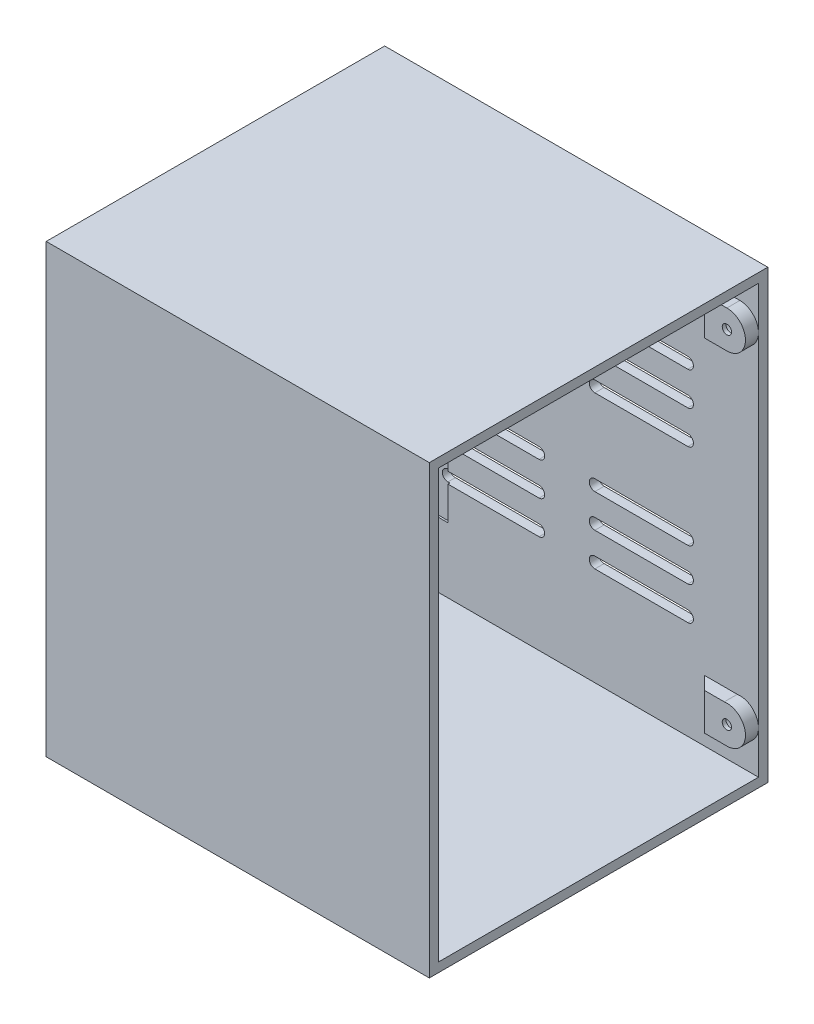
SolidWorks part; units mm, degrees
ref_plane "Front Plane" through (0, 0, 0) normal (0, 0, 1) x (1, 0, 0)
ref_plane "Top Plane" through (0, 0, 0) normal (0, 1, 0) x (1, 0, 0)
ref_plane "Right Plane" through (0, 0, 0) normal (1, 0, 0) x (0, 0, -1)
sketch "Sketch1" plane through (205.5525, 0, 0) normal (1, 0, 0) x (0, 0, -1)
  line L0 (1.5129, 48.8646) -> (1.513, -71.1354) construction
  line L1 (-89.4871, 48.8644) -> (1.5129, 48.8646) construction
  line L2 (-89.4871, 48.8644) -> (-89.487, -71.1356) construction
  line L3 (-89.487, -71.1356) -> (1.513, -71.1354) construction
  line L4 (1.5129, 48.8646) -> (1.513, -71.1354)
  line L5 (-89.4871, 48.8644) -> (1.5129, 48.8646)
  line L6 (-89.4871, 48.8644) -> (-89.487, -71.1356)
  line L7 (-89.487, -71.1356) -> (1.513, -71.1354)
  line L8 (-86.987, -68.6356) -> (-0.987, -68.6355)
  line L9 (-0.9871, 46.3645) -> (-0.987, -68.6355)
  line L10 (-86.9871, 46.3644) -> (-0.9871, 46.3645)
  line L11 (-86.9871, 46.3644) -> (-86.987, -68.6356)
  dimension "D1" = 2.5
extrude "Boss-Extrude1" add sketch "Sketch1" along normal up to surface (103 mm away)
sketch "Sketch2" plane through (0, 0, 86.9871) normal (0, 0, -1) x (-1, 0, 0)
  line L0 (-205.5525, 46.3645) -> (-205.5525, -68.6355) construction
  line L1 (-208.4525, -46.1353) -> (-206.5525, -46.1353)
  line L2 (-208.4525, -46.1353) -> (-208.4525, -40.1355)
  line L3 (-208.4525, -40.1355) -> (-206.5525, -40.1355)
  line L4 (-206.5525, -46.1353) -> (-206.5525, -40.1355)
  line L5 (-206.5525, 23.8645) -> (-208.4525, 23.8645)
  line L6 (-206.5525, 23.8645) -> (-206.5525, 17.8647)
  line L7 (-206.5525, 17.8647) -> (-208.4525, 17.8647)
  line L8 (-208.4525, 23.8645) -> (-208.4525, 17.8647)
  dimension "D1" = 0.1
  dimension "D2" = 1
  dimension "D3" = 0.1
  dimension "D4" = 1
  dimension "D5" = 0
  dimension "D6" = 0
  dimension "D7" = 0
  dimension "D8" = 0
extrude "Boss-Extrude2" add sketch "Sketch2" along normal offset from surface (1.3 mm away) 0.2
sketch "Sketch3" plane through (0, 0, 0.9871) normal (0, 0, 1) x (1, 0, 0)
  line L1 (210.0525, 28.8645) -> (225.0525, 28.8645)
  line L2 (210.0525, 28.8645) -> (210.0525, -51.1355)
  line L3 (210.0525, -51.1355) -> (225.0525, -51.1355)
  line L4 (225.0525, 28.8645) -> (225.0525, -51.1355)
  line L6 (205.5525, -68.6355) -> (205.5525, 46.3645) construction
  line L7 (308.5525, -71.1355) -> (205.5525, -71.1355) construction
  line L8 (308.5525, 48.8645) -> (205.5525, 48.8645) construction
  dimension "D1" = 4.5
  dimension "D2" = 15
  dimension "D3" = 20
  dimension "D4" = 20
extrude "Cut-Extrude1" cut sketch "Sketch3" against normal blind 0.5
sketch "Sketch4" plane through (0, 0, 0.9871) normal (0, 0, 1) x (1, 0, 0)
  line L0 (211.5525, 39.8645) -> (205.5525, 39.8645)
  line L1 (205.5525, -68.6355) -> (205.5525, 46.3645) construction
  line L2 (211.5525, 29.8645) -> (205.5525, 29.8645)
  line L3 (205.5525, 29.8645) -> (205.5525, 39.8645)
  line L4 (211.5525, -52.1355) -> (205.5525, -52.1355)
  line L5 (211.5525, -62.1355) -> (205.5525, -62.1355)
  line L6 (205.5525, -62.1355) -> (205.5525, -52.1355)
  line L7 (303.5525, -62.1355) -> (293.5525, -62.1355)
  line L8 (293.5525, -62.1355) -> (293.5525, -52.1855)
  line L9 (303.6025, -52.1855) -> (293.5525, -52.1855)
  line L10 (303.5525, 29.8645) -> (293.5525, 29.8645)
  line L11 (303.5525, 39.8645) -> (293.5525, 39.8645)
  line L12 (293.5525, 39.8645) -> (293.5525, 29.8645)
  circle A0 centre (211.5525, 34.8645) radius 2.25 construction
  circle A1 centre (211.5525, -57.1355) radius 2.25 construction
  circle A2 centre (211.5525, 34.8645) radius 2.25 construction
  circle A3 centre (211.5525, -57.1355) radius 2.25 construction
  circle A4 centre (211.5525, -57.1355) radius 5
  circle A5 centre (211.5525, 34.8645) radius 5
  circle A6 centre (211.5525, -57.1355) radius 3.5
  circle A7 centre (211.5525, 34.8645) radius 3.5
  circle A8 centre (211.5525, 34.8645) radius 1.25
  circle A9 centre (211.5525, -57.1355) radius 1.25
  circle A10 centre (303.5525, 34.8645) radius 1.6 construction
  circle A11 centre (303.5525, -57.1355) radius 1.6 construction
  circle A12 centre (303.5525, 34.8645) radius 1.6 construction
  circle A13 centre (303.5525, -57.1355) radius 1.6 construction
  circle A14 centre (303.5525, 34.8645) radius 5
  circle A15 centre (303.5525, -57.1355) radius 5
  circle A16 centre (303.5525, -57.1355) radius 3.5
  circle A17 centre (303.5525, -57.1355) radius 1.25
  circle A18 centre (303.5525, 34.8645) radius 3.5
  circle A19 centre (303.5525, 34.8645) radius 1.25
  line M7 (205.5525, 46.3645) -> (205.5525, -68.6355)
  dimension "D1" = 10
  dimension "D2" = 10
  dimension "D3" = 7
  dimension "D4" = 7
  dimension "D5" = 2.5
  dimension "D6" = 2.5
  dimension "D7" = 10
  dimension "D8" = 7
  dimension "D9" = 2.5
  dimension "D10" = 10
  dimension "D11" = 7
  dimension "D12" = 2.5
  dimension "D13" = 10
  dimension "D14" = 10
extrude "Boss-Extrude3" add sketch "Sketch4" along normal up to surface (3.5 mm away) contours A5 A7 | A4 A6 | A5 L0 L2 M7 | A4 L4 L5 M7 | A15 A16 | A14 A18 | A14 L11 L12 L10 | A15 L9 L8 L7 region at (206.4359, 34.8645, 0.9871) region at (208.5525, -52.2521, 0.9871) region at (214.988, 38.3001, 0.9871) region at (214.988, -53.6999, 0.9871) region at (298.7061, -57.479, 0.9871) region at (296.6787, -57.1748, 0.9871) region at (296.6915, 34.8645, 0.9871) region at (298.6939, 34.8645, 0.9871)
extrude "Boss-Extrude4" add sketch "Sketch4<3>" against normal blind 1 from surface contours A7 A8 | A18 A19 | A16 A17 | A6 A9 region at (208.1515, -57.1355, 0.9871) region at (208.1515, 34.8645, 0.9871) region at (300.1515, -57.1355, 0.9871) region at (300.1515, 34.8645, 0.9871) starting at face at (307.0525, 34.8645, 4.4871)
sketch "Sketch4<3>" plane through (0, 0, 0.9871) normal (0, 0, 1) x (1, 0, 0) same geometry as "Sketch4"
extrude "Cut-Extrude2" cut sketch "Sketch4<4>" against normal through all contours A6 A9 | A9 | A7 A8 | A8 | A17 | A16 A17 | A19 | A18 A19 region at (208.1515, -57.1355, 0.9871) region at (208.1515, 34.8645, 0.9871) region at (211.5525, 34.8645, 0.9871) region at (211.5525, -57.1355, 0.9871) region at (300.1515, -57.1355, 0.9871) region at (303.5525, -57.1355, 0.9871) region at (300.1515, 34.8645, 0.9871) region at (303.5525, 34.8645, 0.9871)
sketch "Sketch4<4>" plane through (0, 0, 0.9871) normal (0, 0, 1) x (1, 0, 0) same geometry as "Sketch4"
chamfer "Chamfer1" distance 4 angle 45 1 edges at (293.5525, -57.1605, 4.4871)
chamfer "Chamfer2" distance 4 angle 45 1 edges at (293.5525, 34.8645, 4.4871)
sketch "Sketch5" plane through (0, 0, -1.5129) normal (0, 0, -1) x (-1, 0, 0)
  line L0 (-257.0525, 48.8645) -> (-257.0525, -71.1355) construction
  line L1 (-308.5525, 48.8645) -> (-205.5525, 48.8645) construction
  line L2 (-308.5525, -71.1355) -> (-205.5525, -71.1355) construction
  line L3 (-308.5525, -11.1355) -> (-205.5525, -11.1355) construction
  line L4 (-308.5525, -71.1355) -> (-308.5525, 48.8645) construction
  line L5 (-205.5525, 48.8645) -> (-205.5525, -71.1355) construction
  line L6 (-289.5525, 10.8645) -> (-289.5525, 7.8645)
  line L7 (-289.5525, 1.8645) -> (-264.5525, 1.8645)
  line L8 (-289.5525, 1.8645) -> (-289.5525, -1.1355)
  line L9 (-289.5525, -1.1355) -> (-264.5525, -1.1355)
  line L10 (-264.5525, 1.8645) -> (-264.5525, -1.1355)
  line L11 (-289.5525, 10.8645) -> (-264.5525, 10.8645)
  line L12 (-264.5525, 10.8645) -> (-264.5525, 7.8645)
  line L13 (-289.5525, 7.8645) -> (-264.5525, 7.8645)
  line L14 (-289.5525, 19.8645) -> (-289.5525, 16.8645)
  line L15 (-289.5525, 19.8645) -> (-264.5525, 19.8645)
  line L16 (-264.5525, 19.8645) -> (-264.5525, 16.8645)
  line L17 (-289.5525, 16.8645) -> (-264.5525, 16.8645)
  line L18 (-224.5525, 16.8645) -> (-249.5525, 16.8645)
  line L19 (-249.5525, 19.8645) -> (-249.5525, 16.8645)
  line L20 (-224.5525, 19.8645) -> (-249.5525, 19.8645)
  line L21 (-224.5525, 19.8645) -> (-224.5525, 16.8645)
  line L22 (-224.5525, 7.8645) -> (-249.5525, 7.8645)
  line L23 (-249.5525, 10.8645) -> (-249.5525, 7.8645)
  line L24 (-224.5525, 10.8645) -> (-249.5525, 10.8645)
  line L25 (-249.5525, 1.8645) -> (-249.5525, -1.1355)
  line L26 (-224.5525, -1.1355) -> (-249.5525, -1.1355)
  line L27 (-224.5525, 1.8645) -> (-224.5525, -1.1355)
  line L28 (-224.5525, 1.8645) -> (-249.5525, 1.8645)
  line L29 (-224.5525, 10.8645) -> (-224.5525, 7.8645)
  line L30 (-224.5525, -33.1355) -> (-224.5525, -30.1355)
  line L31 (-224.5525, -24.1355) -> (-249.5525, -24.1355)
  line L32 (-224.5525, -24.1355) -> (-224.5525, -21.1355)
  line L33 (-224.5525, -21.1355) -> (-249.5525, -21.1355)
  line L34 (-249.5525, -24.1355) -> (-249.5525, -21.1355)
  line L35 (-224.5525, -33.1355) -> (-249.5525, -33.1355)
  line L36 (-249.5525, -33.1355) -> (-249.5525, -30.1355)
  line L37 (-224.5525, -30.1355) -> (-249.5525, -30.1355)
  line L38 (-224.5525, -42.1355) -> (-224.5525, -39.1355)
  line L39 (-224.5525, -42.1355) -> (-249.5525, -42.1355)
  line L40 (-249.5525, -42.1355) -> (-249.5525, -39.1355)
  line L41 (-224.5525, -39.1355) -> (-249.5525, -39.1355)
  line L42 (-289.5525, -39.1355) -> (-264.5525, -39.1355)
  line L43 (-264.5525, -42.1355) -> (-264.5525, -39.1355)
  line L44 (-289.5525, -42.1355) -> (-264.5525, -42.1355)
  line L45 (-289.5525, -42.1355) -> (-289.5525, -39.1355)
  line L46 (-289.5525, -30.1355) -> (-264.5525, -30.1355)
  line L47 (-264.5525, -33.1355) -> (-264.5525, -30.1355)
  line L48 (-289.5525, -33.1355) -> (-264.5525, -33.1355)
  line L49 (-264.5525, -24.1355) -> (-264.5525, -21.1355)
  line L50 (-289.5525, -21.1355) -> (-264.5525, -21.1355)
  line L51 (-289.5525, -24.1355) -> (-289.5525, -21.1355)
  line L52 (-289.5525, -24.1355) -> (-264.5525, -24.1355)
  line L53 (-289.5525, -33.1355) -> (-289.5525, -30.1355)
  arc A0 (-264.5525, 1.8645) -> (-264.5525, -1.1355) centre (-264.5525, 0.3645) cw
  arc A1 (-289.5525, -1.1355) -> (-289.5525, 1.8645) centre (-289.5525, 0.3645) cw
  arc A2 (-264.5525, 10.8645) -> (-264.5525, 7.8645) centre (-264.5525, 9.3645) cw
  arc A3 (-289.5525, 7.8645) -> (-289.5525, 10.8645) centre (-289.5525, 9.3645) cw
  arc A4 (-264.5525, 19.8645) -> (-264.5525, 16.8645) centre (-264.5525, 18.3645) cw
  arc A5 (-289.5525, 16.8645) -> (-289.5525, 19.8645) centre (-289.5525, 18.3645) cw
  arc A6 (-224.5525, 16.8645) -> (-224.5525, 19.8645) centre (-224.5525, 18.3645) ccw
  arc A7 (-249.5525, 19.8645) -> (-249.5525, 16.8645) centre (-249.5525, 18.3645) ccw
  arc A8 (-224.5525, 7.8645) -> (-224.5525, 10.8645) centre (-224.5525, 9.3645) ccw
  arc A9 (-249.5525, 10.8645) -> (-249.5525, 7.8645) centre (-249.5525, 9.3645) ccw
  arc A10 (-224.5525, -1.1355) -> (-224.5525, 1.8645) centre (-224.5525, 0.3645) ccw
  arc A11 (-249.5525, 1.8645) -> (-249.5525, -1.1355) centre (-249.5525, 0.3645) ccw
  arc A12 (-249.5525, -24.1355) -> (-249.5525, -21.1355) centre (-249.5525, -22.6355) cw
  arc A13 (-224.5525, -21.1355) -> (-224.5525, -24.1355) centre (-224.5525, -22.6355) cw
  arc A14 (-249.5525, -33.1355) -> (-249.5525, -30.1355) centre (-249.5525, -31.6355) cw
  arc A15 (-224.5525, -30.1355) -> (-224.5525, -33.1355) centre (-224.5525, -31.6355) cw
  arc A16 (-249.5525, -42.1355) -> (-249.5525, -39.1355) centre (-249.5525, -40.6355) cw
  arc A17 (-224.5525, -39.1355) -> (-224.5525, -42.1355) centre (-224.5525, -40.6355) cw
  arc A18 (-289.5525, -39.1355) -> (-289.5525, -42.1355) centre (-289.5525, -40.6355) ccw
  arc A19 (-264.5525, -42.1355) -> (-264.5525, -39.1355) centre (-264.5525, -40.6355) ccw
  arc A20 (-289.5525, -30.1355) -> (-289.5525, -33.1355) centre (-289.5525, -31.6355) ccw
  arc A21 (-264.5525, -33.1355) -> (-264.5525, -30.1355) centre (-264.5525, -31.6355) ccw
  arc A22 (-289.5525, -21.1355) -> (-289.5525, -24.1355) centre (-289.5525, -22.6355) ccw
  arc A23 (-264.5525, -24.1355) -> (-264.5525, -21.1355) centre (-264.5525, -22.6355) ccw
  dimension "D1" = 3
  dimension "D2" = 25
  dimension "D3" = 10
  dimension "D4" = 7.5
  dimension "D6" = 6
  dimension "D5" = 3
extrude "Cut-Extrude3" cut sketch "Sketch5" against normal blind 3 contours L14 L17 L16 L15 | A5 L14 | A4 L16 | A1 L8 | L10 L7 L8 L9 | A0 L10 | A2 L12 | L6 L13 L12 L11 | A3 L6 | A17 L38 | L38 L41 L40 L39 | A16 L40 | A14 L36 | L30 L37 L36 L35 | A15 L30 | A13 L32 | L34 L31 L32 L33 | A12 L34 | L51 A22 | L51 L52 L49 L50 | L49 A23 | L47 A21 | L53 L48 L47 L46 | L53 A20 | L45 A18 | L45 L44 L43 L42 | L43 A19 | L21 A6 | L21 L20 L19 L18 | L19 A7 | L23 A9 | L29 L24 L23 L22 | L29 A8 | L27 A10 | L27 L28 L25 L26 | L25 A11 region at (277.0525, 9.3645, -1.5129) region at (290.1891, 9.3645, -1.5129) region at (263.9159, 9.3645, -1.5129) region at (277.0525, 0.3645, -1.5129) region at (290.1891, 0.3645, -1.5129) region at (263.9159, 0.3645, -1.5129) region at (277.0525, 18.3645, -1.5129) region at (290.1891, 18.3645, -1.5129) region at (263.9159, 18.3645, -1.5129) region at (237.0525, 18.3645, -1.5129) region at (223.9159, 18.3645, -1.5129) region at (250.1891, 18.3645, -1.5129) region at (237.0525, 9.3645, -1.5129) region at (223.9159, 9.3645, -1.5129) region at (250.1891, 9.3645, -1.5129) region at (237.0525, 0.3645, -1.5129) region at (250.1891, 0.3645, -1.5129) region at (223.9159, 0.3645, -1.5129) region at (237.0525, -31.6355, -1.5129) region at (223.9159, -31.6355, -1.5129) region at (250.1891, -31.6355, -1.5129) region at (237.0525, -22.6355, -1.5129) region at (223.9159, -22.6355, -1.5129) region at (250.1891, -22.6355, -1.5129) region at (237.0525, -40.6355, -1.5129) region at (223.9159, -40.6355, -1.5129) region at (250.1891, -40.6355, -1.5129) region at (277.0525, -40.6355, -1.5129) region at (290.1891, -40.6355, -1.5129) region at (263.9159, -40.6355, -1.5129) region at (277.0525, -31.6355, -1.5129) region at (290.1891, -31.6355, -1.5129) region at (263.9159, -31.6355, -1.5129) region at (277.0525, -22.6355, -1.5129) region at (263.9159, -22.6355, -1.5129) region at (290.1891, -22.6355, -1.5129)
equation "\"R\"=9.03994"
equation "\"R_MOUNT_OUTER\"=10"
equation "\"D1@Sketch4\"=\"R_MOUNT_OUTER\""
equation "\"D2@Sketch4\"=\"R_MOUNT_OUTER\""
equation "\"R_MOUNT_INNER\"=7"
equation "\"D3@Sketch4\"=\"R_MOUNT_INNER\""
equation "\"D4@Sketch4\"=\"R_MOUNT_INNER\""
equation "\"R_SCREW\"=2.5"
equation "\"D5@Sketch4\"=\"R_SCREW\""
equation "\"D6@Sketch4\"=\"R_SCREW\""
equation "\"D7@Sketch4\"=\"R_MOUNT_OUTER\""
equation "\"D8@Sketch4\"=\"R_MOUNT_INNER\""
equation "\"D9@Sketch4\"=\"R_SCREW\""
equation "\"D10@Sketch4\"=\"R_MOUNT_OUTER\""
equation "\"D11@Sketch4\"=\"R_MOUNT_INNER\""
equation "\"D12@Sketch4\"=\"R_SCREW\""
